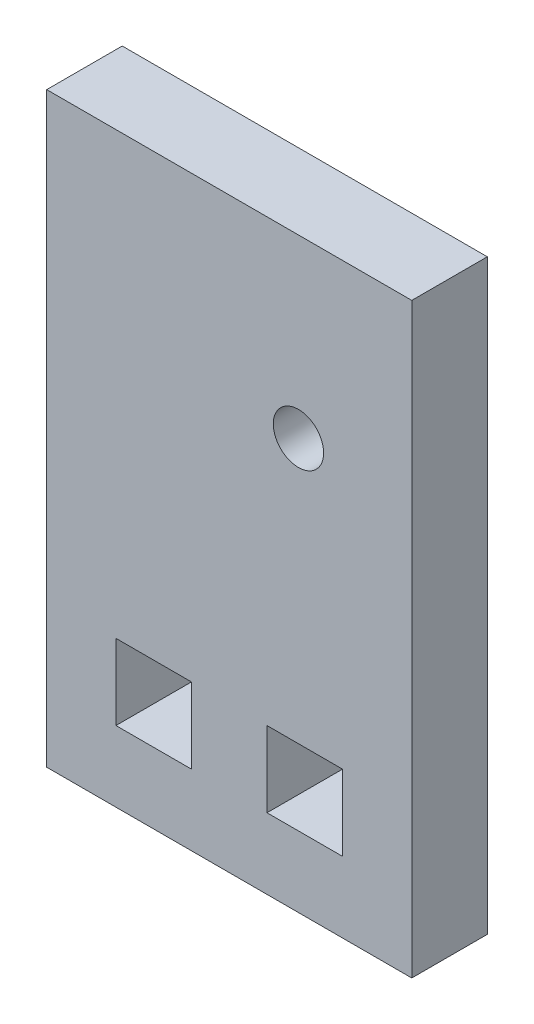
SolidWorks part; units mm, degrees
ref_plane "Front Plane" through (0, 0, 0) normal (0, 0, 1) x (1, 0, 0)
ref_plane "Top Plane" through (0, 0, 0) normal (0, 1, 0) x (1, 0, 0)
ref_plane "Right Plane" through (0, 0, 0) normal (1, 0, 0) x (0, 0, -1)
sketch "Sketch2" plane through (0, 0, 0) normal (0, 0, 1) x (1, 0, 0)
  line L22 (0.2452, 13.1921) -> (0.2452, -7.3032) construction
  line L23 (-7.0048, -7.3079) -> (-7.0048, 13.1921)
  line L24 (-7.0048, 13.1921) -> (7.4952, 13.1921)
  line L25 (7.4952, -7.117) -> (7.4952, 13.1921)
  line L26 (-7.0048, -7.3079) -> (7.4952, 13.1921) construction
  line L27 (-7.0048, 13.1921) -> (7.4952, -7.117) construction
  line L28 (-4.2548, -7.3079) -> (-4.2548, -4.3079)
  line L29 (-4.2548, -4.3079) -> (-1.2548, -4.3079)
  line L30 (-1.2548, -7.3079) -> (-1.2548, -4.3079)
  line L31 (4.7452, -4.3079) -> (1.7452, -4.3079)
  line L32 (1.7452, -7.3079) -> (1.7452, -4.3079)
  line L33 (4.7452, -7.3079) -> (4.7452, -4.3079)
  line L34 (1.7452, -7.3079) -> (4.7452, -7.3079)
  line L35 (-4.2548, -7.3079) -> (-1.2548, -7.3079)
  line L36 (-7.0048, -7.3079) -> (-7.0048, -10.117)
  line L37 (-7.0048, -10.117) -> (7.4952, -10.117)
  line L38 (7.4952, -7.117) -> (7.4952, -10.117)
  circle A1 centre (2.9952, 6.1921) radius 1
  point P13 (0.2791, 2.9901)
  dimension "D19" = 2
  dimension "D10" = 20.5
  dimension "D11" = 3
  dimension "D12" = 3
  dimension "D13" = 1.5
  dimension "D14" = 3
  dimension "D15" = 3
  dimension "D16" = 14.5
  dimension "D17" = 4.5
  dimension "D18" = 7
extrude "Boss-Extrude1" add sketch "Sketch2" along normal blind 3
